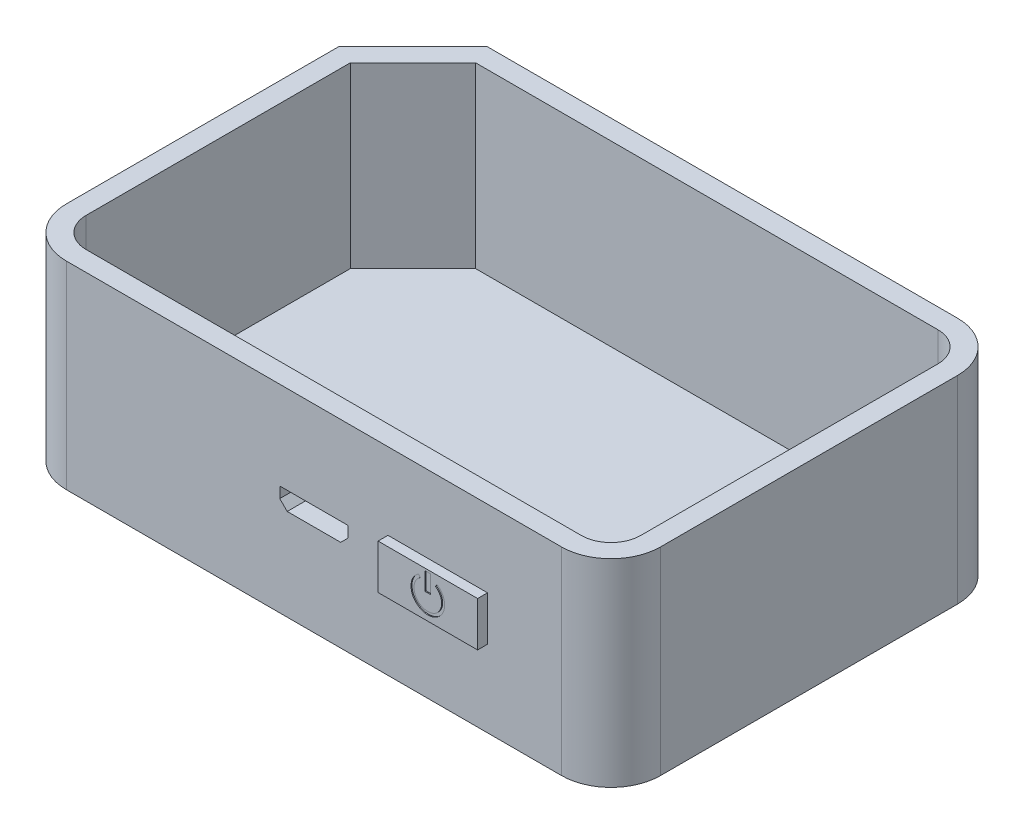
SolidWorks part; units mm, degrees
ref_plane "Front Plane" through (0, 0, 0) normal (0, 0, 1) x (1, 0, 0)
ref_plane "Top Plane" through (0, 0, 0) normal (0, 1, 0) x (1, 0, 0)
ref_plane "Right Plane" through (0, 0, 0) normal (1, 0, 0) x (0, 0, -1)
sketch "Sketch4" plane through (0, 0, 0) normal (0, 1, 0) x (1, 0, 0)
  line L0 (-39.827, 7.6292) -> (20.173, 7.6292)
  line L1 (-39.827, 7.6292) -> (-39.827, -32.3708)
  line L2 (20.173, 7.6292) -> (20.173, -32.3708)
  line L3 (-39.827, -32.3708) -> (20.173, -32.3708)
extrude "Boss-Extrude1" add sketch "Sketch4" along normal blind 20
fillet "Fillet1" radius 5 1 edges at (20.173, 10, 32.3708)
fillet "Fillet2" radius 5 2 edges at (-39.827, 10, 32.3708) (20.173, 10, -7.6292)
sketch "Sketch6" plane through (0, 20, 0) normal (0, 1, 0) x (1, 0, 0)
  line L0 (-39.827, 7.6292) -> (20.173, 7.6292) construction
  line L1 (-9.827, 7.6292) -> (-39.827, 7.6292) construction
  line L2 (-24.827, 7.6292) -> (-39.827, 7.6292) construction
  line L3 (-32.327, 7.6292) -> (-39.827, 7.6292) construction
  line L4 (-32.327, 7.6292) -> (-39.827, 0.1292)
  line L5 (-39.827, 7.6292) -> (-39.827, -27.3708) construction
  line L6 (-32.327, 7.6292) -> (-39.827, 7.6292)
  line L7 (-39.827, 7.6292) -> (-39.827, 0.1292)
extrude "Cut-Extrude1" cut sketch "Sketch6" against normal blind 8
sketch "Sketch7" plane through (0, 0, 0) normal (0, -1, 0) x (1, 0, 0)
  line L0 (-39.827, -7.6292) -> (20.173, -7.6292) construction
  line L1 (-9.827, -7.6292) -> (-39.827, -7.6292) construction
  line L2 (-24.827, -7.6292) -> (-39.827, -7.6292) construction
  line L3 (-32.327, -7.6292) -> (-39.827, -0.1292)
  line L4 (-32.327, -7.6292) -> (-39.827, -7.6292)
  line L5 (-39.827, -7.6292) -> (-39.827, -0.1292)
extrude "Cut-Extrude2" cut sketch "Sketch7" against normal blind 8
sketch "Sketch8" plane through (0, 12, 0) normal (0, 1, 0) x (1, 0, 0)
  line L0 (-36.077, 3.8792) -> (-36.077, 7.6292) construction
  line L2 (-39.827, 3.8792) -> (-32.327, 3.8792) construction
  line L3 (-39.827, 7.6292) -> (-39.827, 0.1292) construction
  line L5 (-39.827, 0.1292) -> (-33.0463, 0.1292) construction
  line L6 (-32.327, 7.6292) -> (-39.827, 7.6292) construction
  line L7 (-36.077, 5.7542) -> (-39.827, 5.7542) construction
  line L8 (-37.9892, 3.8792) -> (-37.9892, 7.6292) construction
  line L9 (-37.952, 5.7542) -> (-36.077, 5.7542) construction
  line L10 (-37.0145, 5.7542) -> (-37.0145, 3.8792) construction
  line L11 (-37.0145, 4.8167) -> (-37.9892, 4.8167) construction
  line L12 (-37.5018, 4.8167) -> (-37.5018, 5.7542) construction
  line L13 (-37.5018, 5.2854) -> (-37.9892, 5.2854) construction
  circle A0 centre (-37.5018, 5.2854) radius 1.5
extrude "Cut-Extrude4" cut sketch "Sketch8" against normal blind 8
shell "Shell3" thickness 2 removed face at (-9.385, 20, 12.8128)
sketch "Sketch9" plane through (0, 0, 32.3708) normal (0, 0, 1) x (1, 0, 0)
  line L0 (-9.827, 20) -> (-9.827, 0) construction
  line L1 (-34.827, 20) -> (15.173, 20) construction
  line L2 (-34.827, 0) -> (15.173, 0) construction
  line L3 (-34.827, 10) -> (-9.827, 10) construction
  line L4 (-34.827, 20) -> (-34.827, 0) construction
  line L5 (-9.827, 10) -> (15.173, 10) construction
  line L6 (15.173, 0) -> (15.173, 20) construction
  line L8 (-2.3519, 7.75) -> (7.698, 7.75)
  line L9 (-2.3519, 7.75) -> (-2.3519, 12.25)
  line L10 (-2.3519, 12.25) -> (7.698, 12.25)
  line L11 (7.698, 7.75) -> (7.698, 12.25)
  line L12 (2.673, 12.25) -> (2.673, 7.75) construction
  line L13 (-2.3519, 10) -> (7.698, 10) construction
  point P10 (2.673, 10)
extrude "Boss-Extrude2" add sketch "Sketch9" along normal blind 1
sketch "Sketch10" plane through (0, 0, 33.3708) normal (0, 0, 1) x (1, 0, 0)
  line L0 (2.673, 10) -> (2.673, 12.25) construction
  line L2 (-2.3519, 7.75) -> (7.698, 7.75) construction
  line L3 (7.698, 10) -> (-2.3519, 10) construction
  line L4 (7.698, 7.75) -> (7.698, 12.25) construction
  line L5 (-2.3519, 12.25) -> (-2.3519, 7.75) construction
  line L6 (1.9027, 11.169) -> (1.7381, 11.4187)
  line L7 (3.4434, 11.169) -> (3.6079, 11.4187)
  line L8 (2.673, 10) -> (2.673, 7.75) construction
  line L9 (7.698, 12.25) -> (-2.3519, 12.25) construction
  line L11 (2.3806, 12.0307) -> (2.9655, 12.0307)
  line L12 (2.3806, 12.0307) -> (2.3806, 10.2193)
  line L13 (2.3806, 10.2193) -> (2.9655, 10.2193)
  line L14 (2.9655, 12.0307) -> (2.9655, 10.2193)
  line L15 (2.673, 10.2193) -> (2.673, 12.0307) construction
  line L16 (2.3806, 11.125) -> (2.9655, 11.125) construction
  arc A0 (1.7381, 11.4187) -> (3.6079, 11.4187) centre (2.673, 10) ccw
  arc A1 (1.9027, 11.169) -> (3.4434, 11.169) centre (2.673, 10) ccw
  point P0 (2.673, 11.125)
extrude "Cut-Extrude5" cut sketch "Sketch10" against normal blind 0.1
sketch "Sketch11" plane through (0, 0, 32.3708) normal (0, 0, 1) x (1, 0, 0)
  line L0 (-34.827, 10) -> (15.173, 10) construction
  line L1 (-34.827, 20) -> (-34.827, 0) construction
  line L2 (15.173, 0) -> (15.173, 20) construction
  line L3 (-9.827, 20) -> (-9.827, 0) construction
  line L4 (-34.827, 20) -> (15.173, 20) construction
  line L5 (-34.827, 0) -> (15.173, 0) construction
  line L6 (-9.827, 10) -> (-6.377, 10) construction
  line L7 (-9.827, 10) -> (-13.277, 10) construction
  line L8 (-9.827, 10) -> (-9.827, 13.45) construction
  line L9 (-13.277, 10) -> (-13.277, 11.1)
  line L10 (-13.277, 11.1) -> (-6.377, 11.1)
  line L11 (-6.377, 11.1) -> (-6.377, 10)
  line L12 (-9.827, 10) -> (-9.827, 9.25) construction
  line L13 (-9.827, 9.25) -> (-7.127, 9.25)
  line L14 (-9.827, 9.25) -> (-12.527, 9.25)
  line L15 (-7.127, 9.25) -> (-6.377, 10)
  line L16 (-12.527, 9.25) -> (-13.277, 10)
extrude "Cut-Extrude6" cut sketch "Sketch11" against normal blind 5.1
sketch "Sketch12" plane through (0, 20, 0) normal (0, 1, 0) x (1, 0, 0)
  line L0 (-37.827, -0.6992) -> (-31.4985, 5.6292)
  line L1 (-31.4985, 5.6292) -> (15.173, 5.6292)
  line L2 (18.173, 2.6292) -> (18.173, -27.3708)
  line L3 (15.173, -30.3708) -> (-34.827, -30.3708)
  line L4 (-34.827, -30.3708) -> (15.173, -30.3708) construction
  line L5 (-34.827, -30.3708) -> (15.173, -30.3708) construction
  line L6 (-37.827, -27.3708) -> (-37.827, -0.6992)
  arc A0 (-37.827, -27.3708) -> (-34.827, -30.3708) centre (-34.827, -27.3708) ccw construction
  arc A1 (-37.827, -27.3708) -> (-34.827, -30.3708) centre (-34.827, -27.3708) ccw construction
  arc A2 (18.173, 2.6292) -> (15.173, 5.6292) centre (15.173, 2.6292) ccw
  arc A4 (-37.827, -27.3708) -> (-34.827, -30.3708) centre (-34.827, -27.3708) ccw
  arc A5 (15.173, -30.3708) -> (18.173, -27.3708) centre (15.173, -27.3708) ccw
